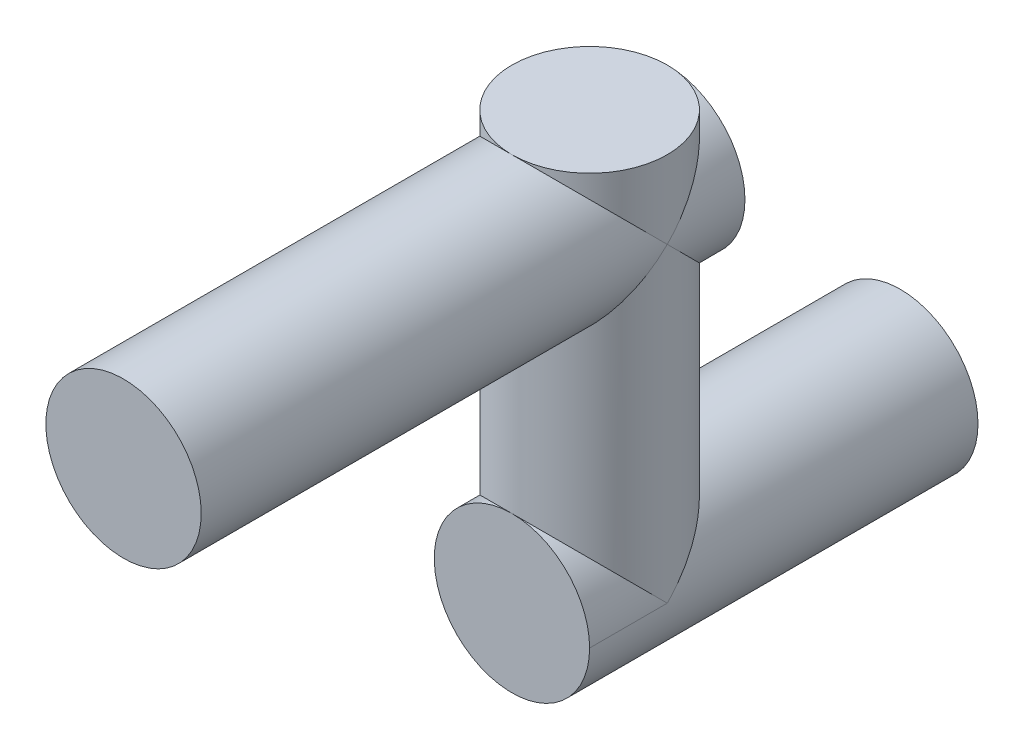
SolidWorks part; units mm, degrees
ref_plane "Front Plane" through (0, 0, 0) normal (0, 0, 1) x (1, 0, 0)
ref_plane "Top Plane" through (0, 0, 0) normal (0, 1, 0) x (1, 0, 0)
ref_plane "Right Plane" through (0, 0, 0) normal (1, 0, 0) x (0, 0, -1)
sketch "Sketch1" plane through (0, 0, 0) normal (0, 0, 1) x (1, 0, 0)
  circle A0 centre (0, 0) radius 10
  dimension "D1" = 20
extrude "Boss-Extrude1" add sketch "Sketch1" along normal blind 50
sketch "Sketch2" plane through (0, 0, 0) normal (0, 1, 0) x (1, 0, 0)
  line L0 (0, -50) -> (0, -33.325) construction
  line L1 (-10, -50) -> (10, -50) construction
  circle A0 centre (0, -40) radius 10
  dimension "D1" = 20
  dimension "D2" = 10
extrude "Boss-Extrude2" add sketch "Sketch2" along normal blind 50
sketch "Sketch4" plane through (0, 0, 0) normal (0, 0, 1) x (1, 0, 0)
  line L0 (0, 50) -> (0, 46.5617) construction
  line L1 (10, 50) -> (-10, 50) construction
  circle A0 centre (0, 40) radius 10
  dimension "D1" = 20
  dimension "D2" = 10
extrude "Boss-Extrude3" add sketch "Sketch4" along normal blind 70 from offset 30
